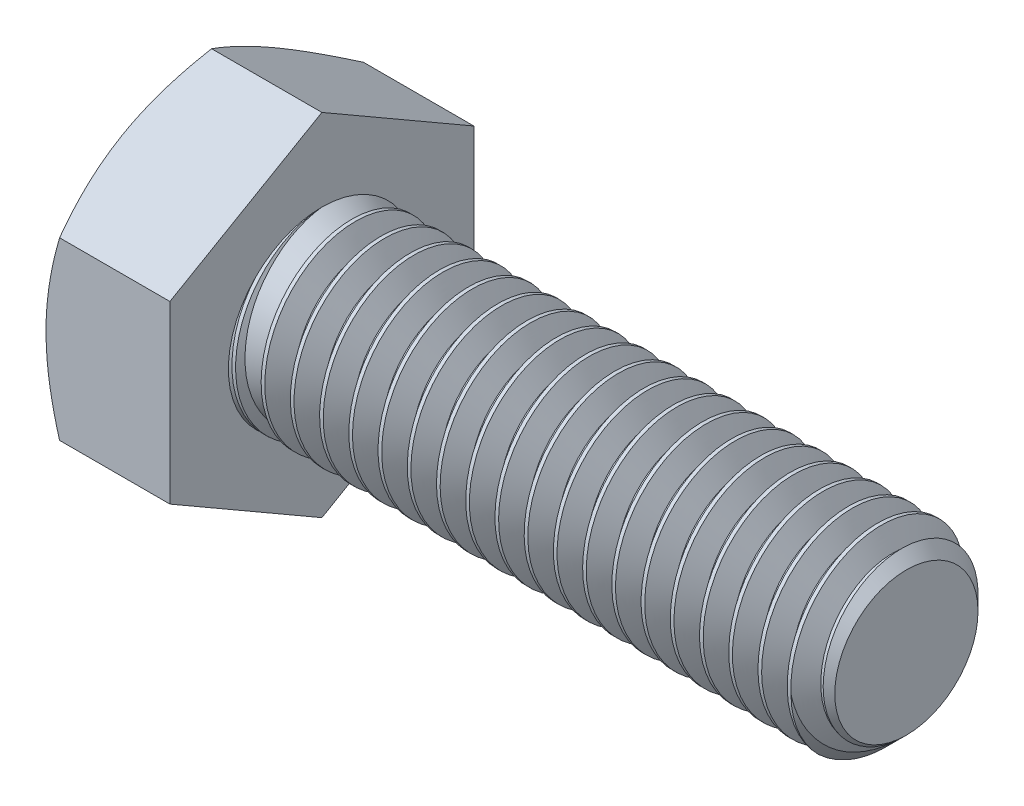
SolidWorks part; units mm, degrees
ref_plane "Front Plane" through (0, 0, 0) normal (0, 0, 1) x (1, 0, 0)
ref_plane "Top Plane" through (0, 0, 0) normal (0, 1, 0) x (1, 0, 0)
ref_plane "Right Plane" through (0, 0, 0) normal (1, 0, 0) x (0, 0, -1)
sketch "Sketch1" plane through (0, 0, 0) normal (0, 0, 1) x (1, 0, 0)
  line L0 (-15.15, 0) -> (15.15, 0) construction
  line L1 (-9.85, 6.5) -> (-9.85, -6.5) construction
  line L2 (-15.15, 6.5) -> (-15.15, -6.5) construction
  line L3 (15.15, 4) -> (15.15, -4) construction
  line L4 (-9.85, -2.8266) -> (-9.85, 4) construction
  line L5 (15.15, 4) -> (-9.85, 4) construction
  point P8 (10.775, -4)
  dimension "D1" = 4.375
  dimension "Thread Dia" = 8
  dimension "D2" = 25
  dimension "Hex" = 13
  dimension "Head Ht" = 5.3
  dimension "Length" = 25
ref_plane "Plane2" through (15.15, 0, 0) normal (1, 0, 0) x (0, 0, -1)
sketch "Sketch2" plane through (15.15, 0, 0) normal (1, 0, 0) x (0, 0, -1)
  circle A0 centre (0, 0) radius 4
extrude "Boss-Extrude1" add sketch "Sketch2" against normal up to vertex (25 mm away) up to point (-9.85, -6.5, 0)
sketch "Sketch4" plane through (15.15, 0, 0) normal (1, 0, 0) x (0, 0, -1)
  circle A1 centre (0, 0) radius 4
  circle A2 centre (0, 0) radius 4
  dimension "D1" = 0
curve "Helix/Spiral1" pitch 1.25 height 26.25 turns 21 parameters "Pitch"=1.25
chamfer "Chamfer1" distance 0.9375 angle 45 1 edges at (15.15, 0, -4)
sketch "Sketch3" plane through (-9.85, 0, 0) normal (-1, 0, 0) x (0, 0, 1)
  line L0 (0, 6.5) -> (0, -6.5) construction
  line L1 (-6.5, -3.7528) -> (0, -7.5056)
  line L2 (0, -7.5056) -> (6.5, -3.7528)
  line L3 (6.5, -3.7528) -> (6.5, 3.7528)
  line L4 (6.5, 3.7528) -> (0, 7.5056)
  line L5 (0, 7.5056) -> (-6.5, 3.7528)
  line L6 (-6.5, 3.7528) -> (-6.5, -3.7528)
  circle A0 centre (0, 0) radius 6.5 construction
extrude "Boss-Extrude2" add sketch "Sketch3" along normal up to vertex (5.3 mm away) separate body up to point (-15.15, -6.5, 0)
sketch "Sketch6" plane through (-15.15, 0, 0) normal (-1, 0, 0) x (0, 0, 1)
  circle A0 centre (0, 0) radius 6.5 construction
  circle A1 centre (0, 0) radius 6.5
extrude "Cut-Extrude1" cut sketch "Sketch6" against normal through all draft 60 flip side to cut
sketch "Sketch7" plane through (-15.15, 0, 0) normal (-1, 0, 0) x (0, 0, 1)
  line L0 (0, 0) -> (0, 6.5) construction
  line L1 (-3.25, 2.1667) -> (3.25, 2.1667) construction
  line L3 (-3.25, 2.1667) -> (-3.25, 5.6292) construction
  line L4 (3.25, 2.1667) -> (3.25, 4.9367) construction
  line L5 (3.25, 4.9367) -> (-3.25, 4.9367) construction
  circle A0 centre (0, 0) radius 6.5 construction
  circle A1 centre (0, 0) radius 6.5 construction
  text T0 "8.8" font "Arial" height 2.7
  point P8 (0, 2.1667)
  dimension "D1" = 13
  dimension "D2" = 6.5
  dimension "D3" = 6.5
  dimension "D4" = 2.1667
  dimension "D5" = 3.4625
  dimension "D6" = 2.77
extrude "Cut-Extrude2" cut sketch "Sketch7" against normal blind 0.5
sketch "Sketch5" plane through (0, 0, 0) normal (0, 0, 1) x (1, 0, 0)
  line L0 (15.15, 4) -> (15.6188, 3.1881)
  line L1 (15.6188, 3.1881) -> (15.775, 3.1881)
  line L2 (15.775, 3.1881) -> (16.2438, 4)
  line L3 (15.15, 4) -> (16.2438, 4)
  line L4 (15.6969, 3.1881) -> (15.6969, 4) construction
  line L5 (15.3844, 3.5941) -> (16.0094, 3.5941) construction
  line L6 (15.15, -4) -> (15.15, 4) construction
  dimension "D1" = 60
  dimension "D2" = 0.1562
  dimension "D3" = 0.625
sweep "Cut-Sweep1" cut profiles "Sketch5" path "Helix/Spiral1"
sketch "Sketch8" plane through (0, 0, 0) normal (0, 0, 1) x (1, 0, 0)
  line L0 (-9.86, 4) -> (-9.85, 4)
  line L1 (-9.85, 4) -> (-2.9218, 0)
  line L2 (-2.9218, 0) -> (-9.86, 0)
  line L3 (-9.86, 0) -> (-9.86, 4)
  line L5 (-15.15, 0) -> (15.15, 0) construction
  line L6 (-9.85, 6.5) -> (-9.85, -6.5) construction
  dimension "D1" = 30
  dimension "Min Thread" = 25
  dimension "D2" = 0.01
revolve "Min Thread" add sketch "Sketch8" angle 360 about L0
combine bodies "Combine1" operation type add bodies to combine 106 105
equation "\"D2@Sketch5\" = \"Pitch@Helix/Spiral1\"*.125"
equation "\"D3@Sketch5\" = \"Pitch@Helix/Spiral1\"*.50"
equation "\"D3@Helix/Spiral1\" = \"Length@Sketch1\"+\"Pitch@Helix/Spiral1\""
equation "\"D1@Chamfer1\" = \"Pitch@Helix/Spiral1\"*.750"
equation "\"D1@Sketch1\" = \"Pitch@Helix/Spiral1\"*3.50"
equation "\"D2@Sketch7\"=\"D1@Sketch7\"/2"
equation "\"D4@Sketch7\"=\"D3@Sketch7\"/3"
equation "\"D6@Sketch7\"=\"D5@Sketch7\"*.8"
equation "\"D2@Sketch1\"= \"Min Thread@Sketch8\""
